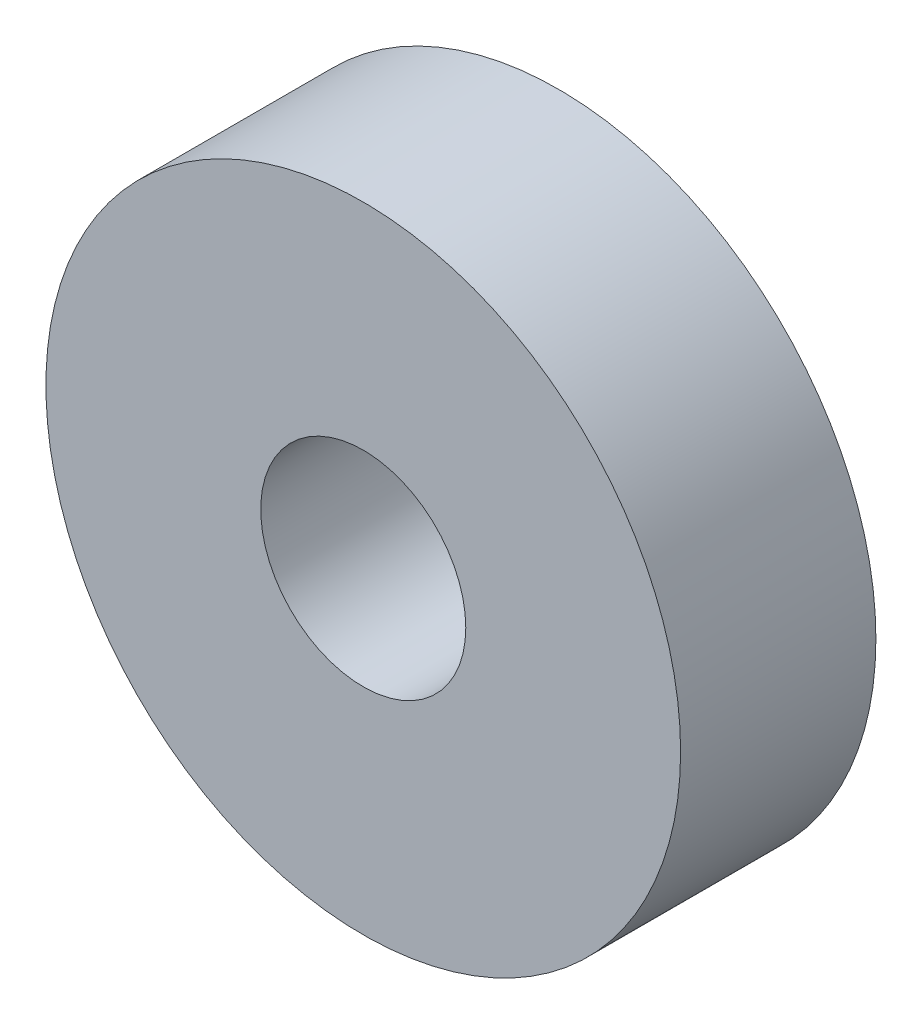
SolidWorks part; units mm, degrees
ref_plane "Front Plane" through (0, 0, 0) normal (0, 0, 1) x (1, 0, 0)
ref_plane "Top Plane" through (0, 0, 0) normal (0, 1, 0) x (1, 0, 0)
ref_plane "Right Plane" through (0, 0, 0) normal (1, 0, 0) x (0, 0, -1)
sketch "Sketch1" plane through (0, 0, 0) normal (0, 0, 1) x (1, 0, 0)
  circle A0 centre (0, 0) radius 6.5
  circle A1 centre (0, 0) radius 2.1
  dimension "OD" = 13
  dimension "ID" = 4.2
extrude "Extrude1" add sketch "Sketch1" along normal mid plane 4
sketch "Sketch2" plane through (0, 0, 0) normal (1, 0, 0) x (0, 0, -1)
  line L0 (-2, -2.1) -> (2, -2.1) construction
  line L3 (2, 2.1) -> (-2, 2.1) construction
  line L5 (-2, -2.1) -> (2, -2.1)
  line L6 (2, 2.1) -> (-2, 2.1)
sketch "Sketch4" plane through (0, 0, 2) normal (0, 0, 1) x (1, 0, 0)
  line L0 (0, 0) -> (-1.4849, 1.4849)
  line L1 (0, -1.1) -> (0, 1.1) construction
  circle A0 centre (0, 0) radius 2.1 construction
  dimension "D1" = 45
